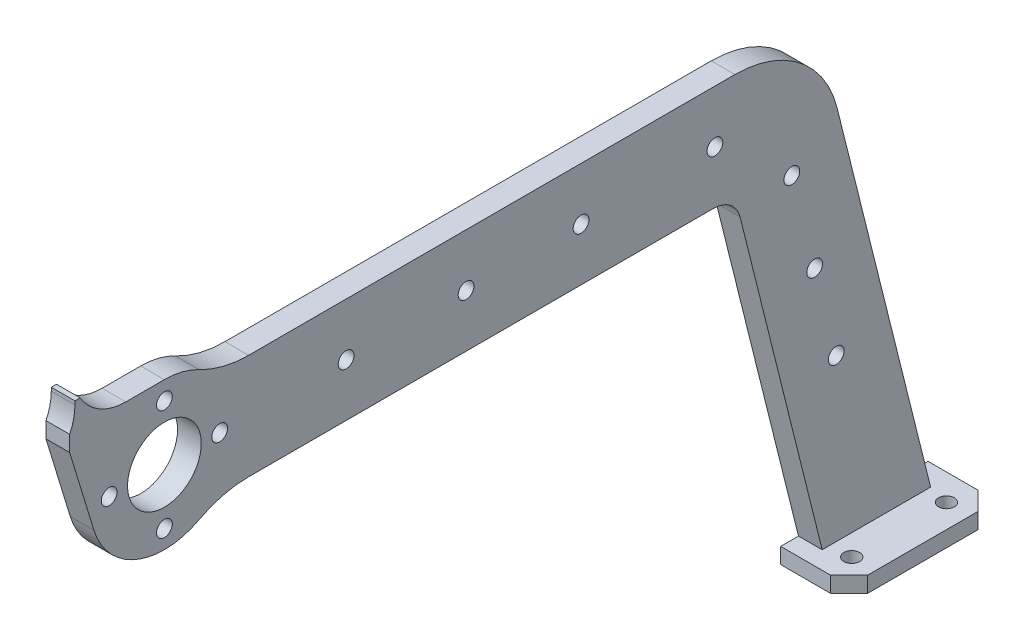
SolidWorks part; units mm, degrees
ref_plane "前视基准面" through (0, 0, 0) normal (0, 0, 1) x (1, 0, 0)
ref_plane "上视基准面" through (0, 0, 0) normal (0, 1, 0) x (1, 0, 0)
ref_plane "右视基准面" through (0, 0, 0) normal (1, 0, 0) x (0, 0, -1)
sketch "草图1" plane through (0, 0, 0) normal (1, 0, 0) x (0, 0, -1)
  line L2 (109.4025, -13.942) -> (125, -76.5)
  line L3 (125, -76.5) -> (145.6123, -76.5)
  line L4 (145.6123, -76.5) -> (127.8256, -5.1616)
  line L5 (108.4197, 10) -> (16, 10)
  line L7 (16, -10) -> (104.357, -10)
  line L8 (135.6657, -77.942) -> (114.3213, 7.6656) construction
  line L9 (0, 14) -> (-18, 14)
  line L10 (-18, 14) -> (-18, 11)
  line L11 (-18, 11) -> (-13.3889, -4.091)
  line L12 (104.357, -15.2) -> (104.357, -10) construction
  arc A0 (6.5882, 12.3529) -> (6.5882, -12.3529) centre (0, 0) ccw
  circle A1 centre (0, 0) radius 10.5 construction
  circle A2 centre (0, 0) radius 7
  circle A3 centre (0, 10.5) radius 1.5
  arc A7 (127.8256, -5.1616) -> (108.4197, 10) centre (108.4197, -10) ccw
  arc A8 (104.357, -10) -> (109.4025, -13.942) centre (104.357, -15.2) cw
  arc A15 (16, 10) -> (6.5882, 12.3529) centre (16, 30) cw
  arc A16 (16, -10) -> (6.5882, -12.3529) centre (16, -30) ccw
  circle A17 centre (10.5, 0) radius 1.5
  circle A18 centre (0, -10.5) radius 1.5
  circle A19 centre (-10.5, 0) radius 1.5
  point P25 (0, 0)
  point P36 (135.3061, -76.5)
  point P43 (9.798, 7.7889)
  point P50 (9.798, -10)
  dimension "D1" = 28
  dimension "D3" = 14
  dimension "D4" = 3
  dimension "D9" = 20
  dimension "D13" = 4
  dimension "D24" = 20
  dimension "D25" = 20
  dimension "D5" = 21
  dimension "D6" = 104
  dimension "D7" = 20
  dimension "D8" = 125
  dimension "D10" = 76.5
  dimension "D11" = 20
  dimension "D12" = 20.6123
  dimension "D14" = 5.2
  dimension "D21" = 18
  dimension "D22" = 3
  dimension "D15" = 88.357
extrude "凸台-拉伸1" add sketch "草图1" along normal mid plane 4.5 contours A16 L7 A8 L2 L3 L4 A7 L5 A15 A0 A18 A17 A3 A2 | A0 L9 L10 L11 | A16 A0 region at (0, -9.6565, -108.6881) region at (0, 9.7023, 13.097)
sketch "草图5" plane through (0, -76.5, 0) normal (0, -1, 0) x (1, 0, 0)
  line L0 (-2.25, -109.4025) -> (-2.25, -125) construction
  line L1 (-2.25, -121.6123) -> (10.75, -121.6123)
  line L2 (-2.25, -121.6123) -> (-2.25, -149.6123)
  line L3 (-2.25, -149.6123) -> (10.75, -149.6123)
  line L4 (10.75, -121.6123) -> (10.75, -149.6123)
  line L5 (2.25, -145.6123) -> (-2.25, -145.6123) construction
  dimension "D1" = 13
  dimension "D2" = 28
  dimension "D3" = 4
extrude "凸台-拉伸3" add sketch "草图5" along normal blind 3
sketch "草图6" plane through (0, -76.5, 0) normal (0, 1, 0) x (1, 0, 0)
  line L0 (10.75, 135.6123) -> (-2.25, 135.6123) construction
  line L1 (10.75, 149.6123) -> (10.75, 121.6123) construction
  line L2 (-2.25, 145.6123) -> (-2.25, 127.8256) construction
  line L5 (2.25, 145.6123) -> (2.25, 127.8256) construction
  circle A0 centre (6.25, 144.6123) radius 1.5
  circle A1 centre (6.25, 126.6123) radius 1.5
  dimension "D3" = 3
  dimension "D1" = 9
  dimension "D2" = 4
extrude "切除-拉伸2" cut sketch "草图6" against normal through all
sketch "草图7" plane through (2.25, 0, 0) normal (1, 0, 0) x (0, 0, -1)
  line L1 (0, 14) -> (-18, 14) construction
  line L2 (-17.0011, 14) -> (-17.0011, 18.9987)
  line L3 (-17.0011, 18.9987) -> (-16.0023, 18.9987)
  line L4 (-16.0023, 18.9987) -> (-16.0023, 14)
  line L5 (-16.0023, 14) -> (-17.0011, 14)
extrude "凸台-拉伸4" add sketch "草图7" against normal up to vertex (4.5 mm away) up to point (-2.25, 14, 0)
fillet "圆角1" radius 10 2 edges at (0, 14, 16.0023) (0, 14, 17.0011)
chamfer "倒角1" distance 3.5 angle 45 2 edges at (10.75, -78, -121.6123) (10.75, -78, -149.6123)
sketch "草图8" plane through (-2.25, 0, 0) normal (-1, 0, 0) x (0, 0, 1)
  line L0 (-16, 10) -> (-16, -10) construction
  line L1 (-108.4197, 10) -> (-104.357, -10) construction
  line L2 (-127.8256, -5.1616) -> (-109.4025, -13.942) construction
  line L3 (-122.5808, -66.797) -> (-141.9867, -61.9586) construction
  line L4 (-109.4025, -13.942) -> (-125, -76.5) construction
  line L5 (-145.6123, -76.5) -> (-127.8256, -5.1616) construction
  line L6 (-132.2837, -64.3778) -> (-118.6141, -9.5518)
  line L7 (-106.3883, 0) -> (-16, 0)
  arc A0 (-104.357, -10) -> (-109.4025, -13.942) centre (-104.357, -15.2) ccw construction
  arc A1 (-118.6141, -9.5518) -> (-106.3883, 0) centre (-106.3883, -12.6) cw
  dimension "D1" = 10
sketch "草图9" plane through (-2.25, 0, 0) normal (-1, 0, 0) x (0, 0, 1)
  line L0 (-132.2837, -64.3778) -> (-118.6141, -9.5518) construction
  line L1 (-106.3883, 0) -> (-16, 0) construction
  point P0 (-127.6641, -45.8494)
  point P1 (-123.5726, -29.4395)
  point P4 (-104.6157, 0)
  point P5 (-79.1822, 0)
  point P8 (-57.3282, 0)
  point P9 (-34.5323, 0)
  point P11 (-119.2336, -12.0366)
sketch "草图10" plane through (-2.25, 0, 0) normal (-1, 0, 0) x (0, 0, 1)
  circle A0 centre (-34.5323, 0) radius 1.5
  dimension "D1" = 3
extrude "切除-拉伸3" cut sketch "草图10" against normal blind 10
pattern_sketch "草图阵列1" of "切除-拉伸3" driven by "草图9"
